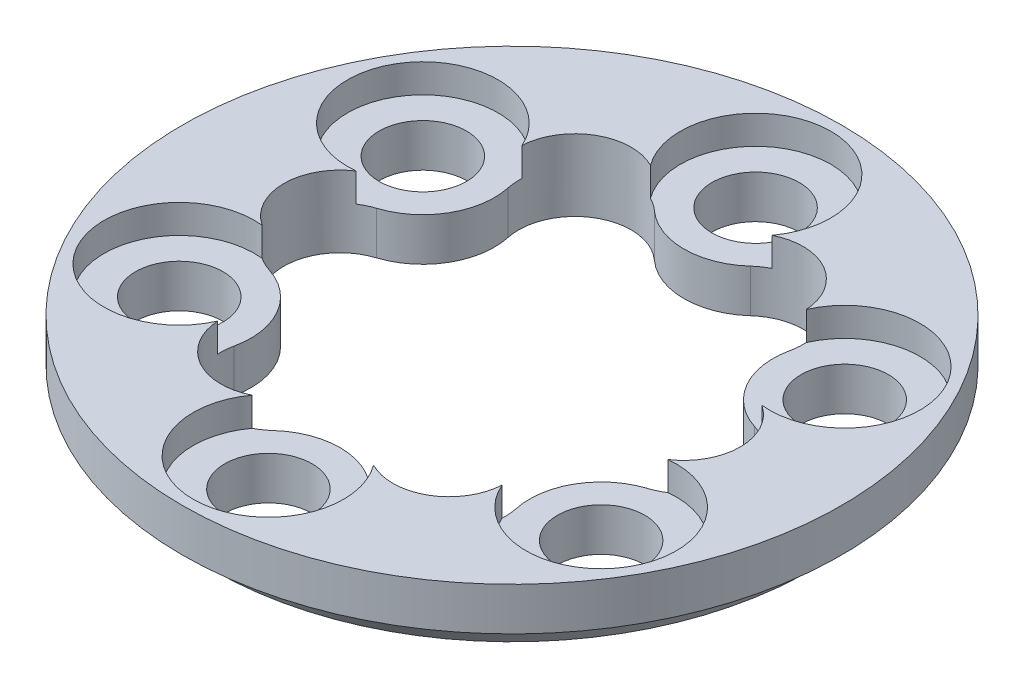
SolidWorks part; units mm, degrees
ref_plane "Front Plane" through (0, 0, 0) normal (0, 0, 1) x (1, 0, 0)
ref_plane "Top Plane" through (0, 0, 0) normal (0, 1, 0) x (1, 0, 0)
ref_plane "Right Plane" through (0, 0, 0) normal (1, 0, 0) x (0, 0, -1)
sketch "Sketch1" plane through (0, 0, 0) normal (0, 1, 0) x (1, 0, 0)
  circle A0 centre (0, 0) radius 23
  circle A1 centre (0, 0) radius 12
  dimension "D1" = 46
  dimension "D2" = 24
extrude "Boss-Extrude1" add sketch "Sketch1" along normal blind 3
sketch "Sketch5" plane through (0, 0, 0) normal (0, -1, 0) x (-1, 0, 0)
  circle A0 centre (0, 0) radius 22
  circle A1 centre (0, 0) radius 12
  dimension "D1" = 24
  dimension "D2" = 44
extrude "Boss-Extrude2" add sketch "Sketch5" along normal blind 2
chamfer "Chamfer1" distance 2 angle 30 1 edges at (0, -2, -22) first distance on face at (0, -2, -22)
sketch "Sketch2" plane through (0, 3, 0) normal (0, 1, 0) x (1, 0, 0)
  circle A0 centre (0, 0) radius 17 construction
  circle A1 centre (0, 17) radius 3.05
  dimension "D1" = 34
  dimension "D2" = 6.1
extrude "Cut-Extrude1" cut sketch "Sketch2" against normal through all
sketch "Sketch7" plane through (0, 3, 0) normal (0, 1, 0) x (1, 0, 0)
  circle A0 centre (0, 17) radius 5.25
  dimension "D1" = 10.5
extrude "Cut-Extrude4" cut sketch "Sketch7" against normal blind 2
pattern_circular "CirPattern1" count 6 over 360 about axis through (0, 3, 0) along (0, 1, 0) of "Cut-Extrude1", "Cut-Extrude4"
sketch "Sketch4" plane through (0, 3, 0) normal (0, 1, 0) x (1, 0, 0)
  line L0 (0, 0) -> (0, 23) construction
  line L1 (0, 0) -> (-19.9186, 11.5) construction
  line L2 (0, 0) -> (-11.5, 19.9186) construction
  line L3 (-10.3923, 6) -> (0, 12)
  arc A0 (-10.3923, 6) -> (-9.8361, 9.5601) centre (-14.7224, 8.5) ccw
  arc A1 (-3.3612, 13.2983) -> (0, 12) centre (0, 17) ccw
  circle A2 centre (0, 0) radius 23 construction
  circle A3 centre (0, 0) radius 12 construction
  arc A4 (-3.3612, 13.2983) -> (-9.8361, 9.5601) centre (-6, 10.3923) ccw
  dimension "D1" = 30
  dimension "D2" = 60
extrude "Cut-Extrude3" cut sketch "Sketch4" against normal through all
pattern_circular "CirPattern3" count 6 over 360 about axis through (0, 3, 0) along (0, 1, 0) of "Cut-Extrude3"
